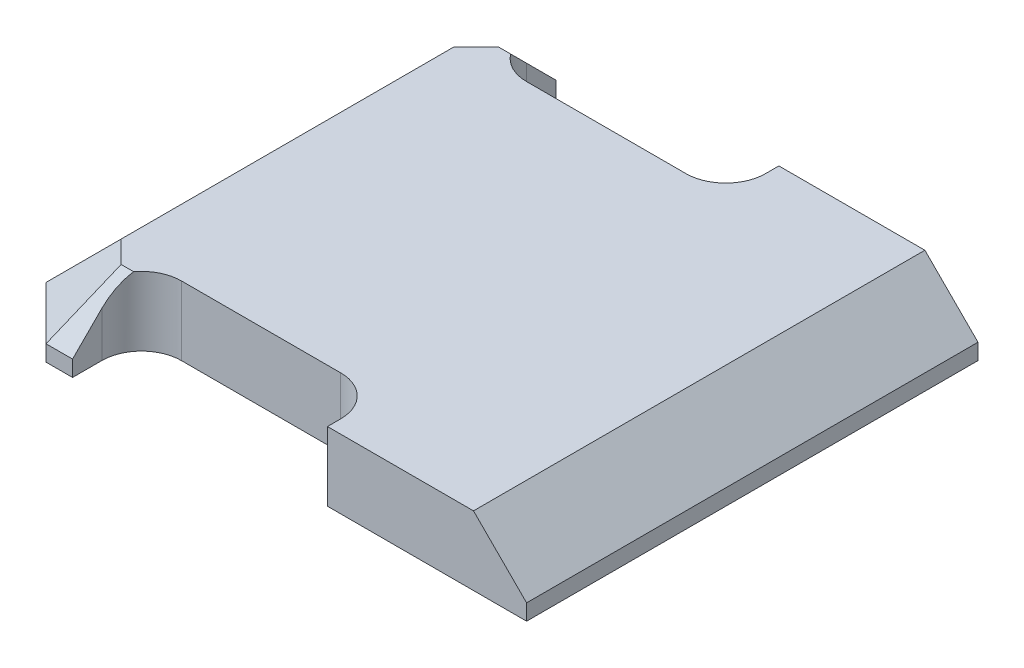
SolidWorks part; units mm, degrees
material "ABS"
ref_plane "Front Plane" through (0, 0, 0) normal (0, 0, 1) x (1, 0, 0)
ref_plane "Top Plane" through (0, 0, 0) normal (0, 1, 0) x (1, 0, 0)
ref_plane "Right Plane" through (0, 0, 0) normal (1, 0, 0) x (0, 0, -1)
sketch "Sketch1" plane through (0, 0, 0) normal (0, 1, 0) x (1, 0, 0)
  line L1 (-97.5, 85) -> (97.5, 85)
  line L2 (-97.5, 85) -> (-97.5, -85)
  line L3 (-97.5, -85) -> (97.5, -85)
  line L4 (97.5, 85) -> (97.5, -85)
  line L5 (-97.5, 85) -> (97.5, -85) construction
  line L6 (-97.5, -85) -> (97.5, 85) construction
  point P0 (0, 0)
  dimension "D1" = 195
  dimension "D2" = 170
extrude "Boss-Extrude1" add sketch "Sketch1" along normal blind 26
sketch "Sketch2" plane through (0, 26, 0) normal (0, 1, 0) x (1, 0, 0)
  line L0 (-97.5, -85) -> (-67.5, -85) construction
  line L1 (-97.5, -85) -> (97.5, -85) construction
  line L2 (0, 0) -> (-97.5, 0) construction
  line L3 (-67.5, -85) -> (22.5, -85)
  line L4 (-67.5, -85) -> (-67.5, -65)
  line L5 (-67.5, -65) -> (22.5, -65)
  line L6 (22.5, -85) -> (22.5, -65)
  line L7 (-97.5, 85) -> (-97.5, -85) construction
  line L8 (-67.5, 65) -> (22.5, 65)
  line L9 (22.5, 85) -> (22.5, 65)
  line L10 (-67.5, 85) -> (22.5, 85)
  line L11 (-67.5, 85) -> (-67.5, 65)
  dimension "D1" = 30
  dimension "D2" = 90
  dimension "D3" = 20
extrude "Cut-Extrude1" cut sketch "Sketch2" against normal through all
fillet "Fillet1" radius 15 4 edges at (22.5, 13, -65) (-67.5, 13, -65) (-67.5, 13, 65) (22.5, 13, 65)
sketch "Sketch3" plane through (0, 26, 0) normal (0, 1, 0) x (1, 0, 0)
  line L0 (0, 0) -> (-97.5, 0) construction
  line L1 (-67.5, 85) -> (-97.5, 85)
  line L2 (-67.5, 85) -> (-67.5, 91)
  line L3 (-67.5, 91) -> (-97.5, 91)
  line L4 (-97.5, 85) -> (-97.5, 91)
  line L5 (-97.5, 85) -> (-97.5, -85) construction
  line L6 (-67.5, -91) -> (-97.5, -91)
  line L7 (-97.5, -85) -> (-97.5, -91)
  line L8 (-67.5, -85) -> (-97.5, -85)
  line L9 (-67.5, -85) -> (-67.5, -91)
  dimension "D1" = 6
extrude "Boss-Extrude2" add sketch "Sketch3" against normal up to surface (26 mm away) up to face at (-16.875, 0, 0)
chamfer "Chamfer1" distance 20 angle 45 2 edges at (-97.5, 13, 91) (-97.5, 13, -91)
chamfer "Chamfer2" distance 20 angle 45 5 edges at (-72.5, 26, 91) (-72.5, 26, -91) (-97.5, 26, 0) (-87.5, 26, 81) (-87.5, 26, -81)
chamfer "Chamfer3" distance 20 angle 45 1 edges at (97.5, 26, 0)
sketch "Sketch4" plane through (-97.5, 0, 0) normal (-1, 0, 0) x (0, 0, 1)
  line L0 (-30.05, 16) -> (30.05, 16) construction
  line L1 (71, 6) -> (-71, 6) construction
  circle A0 centre (-30.05, 16) radius 7
  circle A1 centre (30.05, 16) radius 7
  point P4 (0, 16)
  dimension "D1" = 14
  dimension "D2" = 14
  dimension "D3" = 60.1
  dimension "D4" = 10
sketch "Sketch5" plane through (0, 0, 0) normal (0, -1, 0) x (1, 0, 0)
  line L0 (0, 0) -> (-97.5, 0) construction
  line L1 (-93.5, 37.55) -> (-77.5, 37.55)
  line L2 (-93.5, 37.55) -> (-93.5, 22.55)
  line L3 (-93.5, 22.55) -> (-77.5, 22.55)
  line L4 (-77.5, 37.55) -> (-77.5, 22.55) construction
  line L5 (-93.5, 37.55) -> (-77.5, 22.55) construction
  line L6 (-93.5, 22.55) -> (-77.5, 37.55) construction
  line L7 (-93.5, -22.55) -> (-77.5, -22.55)
  line L8 (-93.5, -22.55) -> (-93.5, -37.55)
  line L9 (-93.5, -37.55) -> (-77.5, -37.55)
  line L10 (-77.5, -22.55) -> (-77.5, -37.55) construction
  line L11 (-93.5, -22.55) -> (-77.5, -37.55) construction
  line L12 (-93.5, -37.55) -> (-77.5, -22.55) construction
  line L13 (-97.5, -71) -> (-97.5, 71) construction
  line L14 (-85.5, 30.05) -> (-85.5, -30.05) construction
  line L15 (-77.5, 37.55) -> (-67.5, 37.55)
  line L16 (-67.5, 37.55) -> (-67.5, -37.55)
  line L17 (-67.5, -37.55) -> (-77.5, -37.55)
  line L18 (-77.5, 22.55) -> (-77.5, -22.55)
  point P0 (-85.5, 30.05)
  point P5 (-85.5, -30.05)
  point P17 (-85.5, 0)
  dimension "D1" = 10
  dimension "D2" = 16
  dimension "D3" = 15
  dimension "D4" = 15
  dimension "D5" = 60.1
  dimension "D6" = 12
extrude "Cut-Extrude3" cut sketch "Sketch5" against normal blind 23
